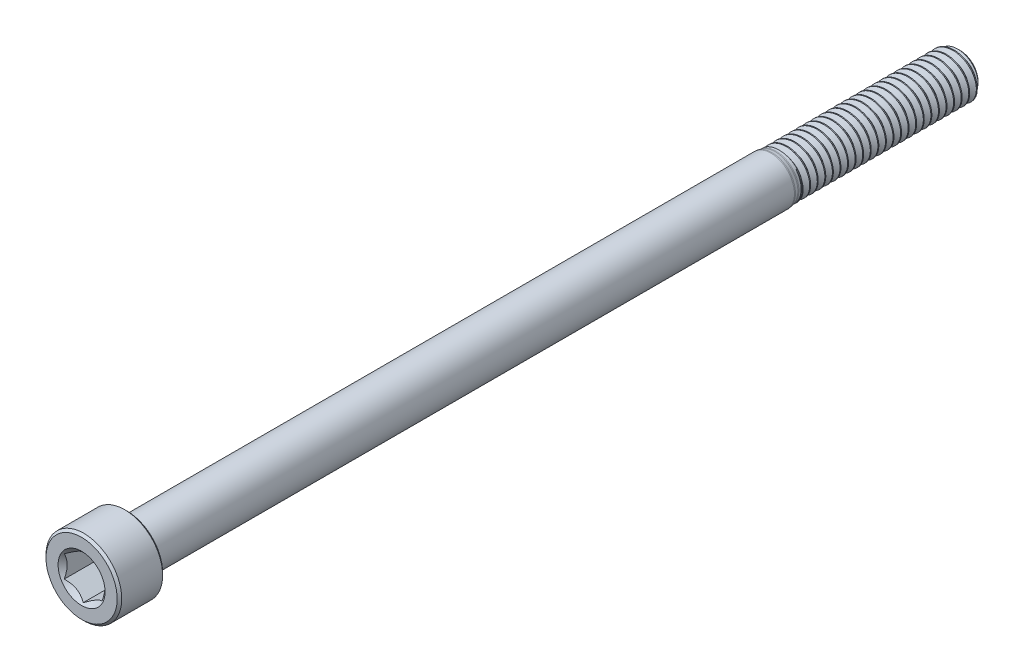
SolidWorks part; units mm, degrees
ref_plane "Front Plane" through (0, 0, 0) normal (0, 0, 1) x (1, 0, 0)
ref_plane "Top Plane" through (0, 0, 0) normal (0, 1, 0) x (1, 0, 0)
ref_plane "Right Plane" through (0, 0, 0) normal (1, 0, 0) x (0, 0, -1)
sketch "Sketch1" plane through (0, 0, 0) normal (1, 0, 0) x (0, 0, -1)
  line L0 (-58, 0) -> (58, 0) construction
  line L1 (58, 0) -> (58, 2.3505) construction
  line L2 (58, 2.3505) -> (57.3505, 3) construction
  line L3 (57.3505, 3) -> (57.25, 3) construction
  line L4 (57.25, 3) -> (-52, 3) construction
  line L5 (-52, 3) -> (-52, 5) construction
  line L6 (-52, 5) -> (-58, 5) construction
  line L7 (-58, 5) -> (-58, 0) construction
  line L8 (58, 2.3505) -> (58, 3) construction
  line L9 (57.9375, 3.1083) -> (58.4375, 2.2422) construction
  line L10 (58.4375, 2.2422) -> (58.9375, 3.1083) construction
  line L11 (58.9375, 3.1083) -> (57.9375, 3.1083) construction
  line L12 (58.4375, 3.1083) -> (58.4375, 3) construction
  line L13 (58.4375, 2.2422) -> (58.4375, 2.3505) construction
  line L14 (58.375, 2.3505) -> (58.5, 2.3505) construction
  line L15 (58, 3) -> (58.875, 3) construction
  line L16 (57.9688, 3.0541) -> (58.9063, 3.0541) construction
  line L17 (58, 0) -> (58, -3) construction
  line L18 (-52.3, 5) -> (-52, 4.7) construction
  line L19 (-57.7, 5) -> (-58, 4.7) construction
  line L20 (-52, 3) -> (-52, 0) construction
  line L21 (-52, 1.5) -> (-15.3333, 1.5) construction
  line L22 (-15.3333, 1.5) -> (21.3333, 1.5) construction
  line L23 (21.3333, 1.5) -> (58, 1.5) construction
  line L24 (-15.3333, 1.5) -> (-15.3333, 3) construction
  line L25 (-15.3333, 3) -> (-15.3333, 5) construction
  line L26 (21.3333, 1.5) -> (21.3333, 5) construction
  point P0 (-58, 2.5)
  point P3 (55.5, 3)
  point P4 (0, 0)
  point P18 (21.3333, 3)
  point P22 (58.4375, 2.3505)
  point P24 (57.25, 3)
  point P25 (58.4375, 3)
  point P28 (58.4375, 3.0541)
  point P29 (55.5, -3)
  point P30 (-15.3333, 3)
  point P31 (-55, 5)
  point P37 (-53.05, 5)
  point P38 (-57.55, 5)
  point P45 (-15.3333, 1.5)
  point P46 (21.3333, 1.5)
  point P49 (34, 3)
  dimension "D1" = 45
  dimension "D2" = 0.125
  dimension "D7" = 0.3
  dimension "D8" = 0.3
  dimension "D9" = 0.3
  dimension "D10" = 0.15
  dimension "D11" = 0.75
  dimension "Drive Size" = 5
  dimension "Head Diameter" = 10
  dimension "Head Height" = 6
  dimension "Thread Pitch" = 1
  dimension "Thread Dia" = 6
  dimension "Length" = 110
  dimension "D12" = 0.75
  dimension "D4" = 2.5
  dimension "Minimum Thread Length" = 24
  dimension "D3" = 86
sketch "Sketch2" plane through (0, 0, 0) normal (1, 0, 0) x (0, 0, -1)
  line L0 (-58, 0) -> (-58, 4.7)
  line L1 (-57.7, 5) -> (-52.3, 5)
  line L2 (-52, 4.7) -> (-52, 3.4083)
  line L4 (57.3505, 3) -> (58, 2.3505)
  line L5 (58, 2.3505) -> (58, 0)
  line L6 (-52, 5) -> (-58, 5) construction
  line L7 (58, 0) -> (-58, 0)
  line L8 (-57.7, 5) -> (-58, 4.7) construction
  line L10 (-57.7, 5) -> (-58, 4.7)
  line L14 (-52.3, 5) -> (-52, 4.7) construction
  line L16 (-52.3, 5) -> (-52, 4.7)
  line L17 (-52, 3) -> (-52, 5) construction
  line L18 (-51.7, 3.1083) -> (33.0069, 3.1083)
  line L19 (33.6989, 3) -> (57.3505, 3)
  line L20 (57.25, 3) -> (-52, 3) construction
  line L21 (33.1532, 3.0938) -> (33.5526, 3.0144)
  line L22 (58.9375, 3.1083) -> (57.9375, 3.1083) construction
  arc A1 (-52, 3.4083) -> (-51.7, 3.1083) centre (-51.7, 3.4083) ccw
  arc A2 (33.0069, 3.1083) -> (33.1532, 3.0938) centre (33.0069, 2.3583) cw
  arc A3 (33.5526, 3.0144) -> (33.6989, 3) centre (33.6989, 3.75) ccw
  point P39 (33.625, 3)
  dimension "D3" = 0.3
  dimension "D6" = 0.75
  dimension "D4" = 11.25
  dimension "D5" = 0.375
revolve "Revolve1" add sketch "Sketch2" angle 360 about L7
sketch "Sketch3" plane through (0, 0, 58) normal (0, 0, 1) x (1, 0, 0)
  line L1 (2.5, -1.4434) -> (2.5, 1.4434)
  line L2 (2.5, 1.4434) -> (0, 2.8868)
  line L3 (0, 2.8868) -> (-2.5, 1.4434)
  line L4 (-2.5, 1.4434) -> (-2.5, -1.4434)
  line L5 (-2.5, -1.4434) -> (0, -2.8868)
  line L6 (0, -2.8868) -> (2.5, -1.4434)
  circle A0 centre (0, 0) radius 2.5 construction
  circle A1 centre (0, 0) radius 5 construction
  circle A2 centre (0, 0) radius 5 construction
  circle A3 centre (0, 0) radius 2.8868 construction
  dimension "D1" = 5.7735
extrude "Cut-Extrude1" cut sketch "Sketch3" against normal offset from surface (5 mm away) 1 up to face at (0, 4.7, 52)
sketch "Sketch4" plane through (0, 0, 58) normal (0, 0, 1) x (1, 0, 0)
  circle A0 centre (0, 0) radius 3.1033
  dimension "D1" = 6.2065
extrude "Cut-Extrude2" cut sketch "Sketch4" against normal up to vertex (3 mm away) draft 45 up to point (0, 5, 55)
sketch "Sketch11" plane through (0, 0, 0) normal (1, 0, 0) x (0, 0, -1)
  line L0 (-58, 0) -> (58, 0) construction
  line L1 (-58, 0) -> (58, 0) construction
  line L2 (-44.475, 0) -> (-44.475, 3) construction
  line L3 (57.25, 3) -> (-52, 3) construction
  line L4 (25.4819, 0) -> (25.4819, 3) construction
  point P2 (-44.475, 0)
  point P3 (25.4819, 0)
  dimension "D1" = 7.525
  dimension "D2" = 7.525
sketch "Sketch6" plane through (0, 0, -58) normal (0, 0, -1) x (-1, 0, 0)
  circle A0 centre (0, 0) radius 3
curve "Helix/Spiral1" pitch 1 height 25 radius 3 centre (0, 0, -58) axis (0, 0, 1) start towards (0, 1, 0)
sketch "Sketch10" plane through (0, 0, 0) normal (1, 0, 0) x (0, 0, -1)
  line L0 (34, -3) -> (34, 3)
  line L2 (-58, 0) -> (58, 0) construction
  point P3 (34, 0)
split "Split1" trim tools "Sketch10" bodies to split 106 resulting bodies 114 115
sketch "Sketch7" plane through (0, 0, 0) normal (1, 0, 0) x (0, 0, -1)
  line L0 (57.9688, 3.0541) -> (58.9063, 3.0541)
  line L1 (58.9063, 3.0541) -> (58.5, 2.3505)
  line L2 (58.5, 2.3505) -> (58.375, 2.3505)
  line L3 (58.375, 2.3505) -> (57.9688, 3.0541)
sweep "Cut-Sweep1" cut profiles "Sketch7" path "Helix/Spiral1" align with end faces yes
sketch "Sketch8" plane through (0, 0, 0) normal (1, 0, 0) x (0, 0, -1)
  line L0 (-52, 0) -> (-52, 3)
  line L2 (-52, 3) -> (34, 3)
  line L4 (34, 3) -> (35.7321, 0)
  line L5 (35.7321, 0) -> (-52, 0)
  line L6 (57.25, 3) -> (-52, 3) construction
  line L7 (-58, 0) -> (58, 0) construction
  dimension "D1" = 60
  dimension "D2" = 24
revolve "Revolve2" add sketch "Sketch8" angle 360 about L5
equation "\"D2@Sketch1\" = \"Thread Pitch@Sketch1\" / 8"
equation "\"D4@Helix/Spiral1\" = \"Thread Pitch@Sketch1\""
equation "\"D7@Sketch1\" = \"Head Height@Sketch1\" * .05"
equation "\"D8@Sketch1\"=\"D7@Sketch1\""
equation "\"D9@Sketch1\"=\"D7@Sketch1\""
equation "\"D10@Sketch1\"=\"D7@Sketch1\"/2"
equation "\"D11@Sketch1\"=\"D10@Sketch1\"*5"
equation "\"D4@Sketch1\"=\"Thread Pitch@Sketch1\"*2.5"
equation "\"D12@Sketch1\"=\"Thread Pitch@Sketch1\"*.75"
equation "\"D3@Helix/Spiral1\"=\"Minimum Thread Length@Sketch1\"+\"Thread Pitch@Sketch1\""
equation "\"D2@Sketch8\"=\"Minimum Thread Length@Sketch1\""
equation "\"D3@Sketch2\"=\"Thread Dia@Sketch1\"*0.05"
equation "\"D5@Sketch2\"=\"D12@Sketch1\"*0.5"
equation "\"D6@Sketch2\"=\"Thread Dia@Sketch1\"*0.125"
equation "\"D1@Sketch11\"=\"D3@Sketch1\"*0.0875"
equation "\"D2@Sketch11\"=\"D1@Sketch11\""
equation "\"D1@Sketch4\"=\"D1@Sketch3\"*1.075"
